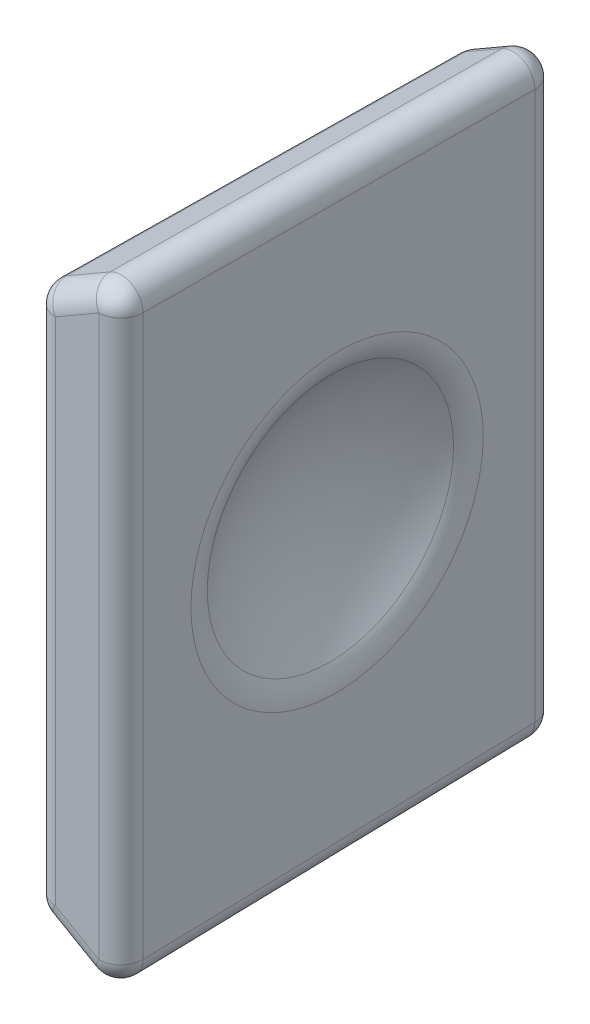
SolidWorks part; units mm, degrees
ref_plane "Front Plane" through (0, 0, 0) normal (0, 0, 1) x (1, 0, 0)
ref_plane "Top Plane" through (0, 0, 0) normal (0, 1, 0) x (1, 0, 0)
ref_plane "Right Plane" through (0, 0, 0) normal (1, 0, 0) x (0, 0, -1)
sketch "Sketch1" plane through (0, 0, 0) normal (0, 0, 1) x (1, 0, 0)
  line L0 (-4, 12.1906) -> (-4, -12.1906)
  line L1 (-4, 12.1906) -> (0, 14.5)
  line L2 (0, 14.5) -> (0, -14.5)
  line L15 (0, -14.5) -> (-4, -12.1906)
  line L50 (0, -14.5) -> (0, -5.2931) construction
  line L53 (0, 1.4892) -> (0, 14.5) construction
  dimension "D2" = 60
  dimension "D1" = 60
  dimension "D3" = 29
  dimension "D4" = 4
extrude "Boss-Extrude1" add sketch "Sketch1" against normal blind 20 draft 0.5 contours L15 L2 L0 region at (-1.9423, 0, 0)
fillet "Fillet1" radius 1 12 edges at (-0.0873, 14.3488, -10) (-0.0873, -14.3488, -10) (-3.9127, -12.1402, -10) (-3.9127, 12.1402, -10) (-3.8255, 0, -20) (-0.1745, 0, -20) (-2, -13.1438, -20) (-4, 0, 0) (0, 0, 0) (-2, -13.3453, 0) (-2, 13.1438, -20) (-2, 13.3453, 0)
sketch "Sketch2" plane through (0, 0, 0) normal (0, 1, 0) x (1, 0, 0)
  line L0 (0, 0) -> (0, 10.0007)
  line L1 (0, 10.0007) -> (8.7268, 10.0007)
  line L2 (8.7268, 20.7276) -> (8.7268, -0.7261)
  line L3 (-0.6702, 20) -> (-0.1702, 20)
  line L4 (-0.1702, 20) -> (0, 10.0007)
  circle A0 centre (8.7268, 10.0007) radius 10.7268
  arc A1 (-0.1702, 19.5044) -> (-0.6702, 20) centre (-0.6702, 19.5) ccw construction
  arc A2 (-0.1702, 19.5044) -> (-0.6702, 20) centre (-0.6702, 19.5) ccw construction
  point P5 (-2, 10.0007)
  dimension "D1" = 2
revolve "Cut-Revolve1" cut sketch "Sketch2" angle 360 about L2 region at (13.2794, 0, -10.0007)
fillet "Fillet2" radius 2 1 edges at (-0.14, 0, -16.0377)
